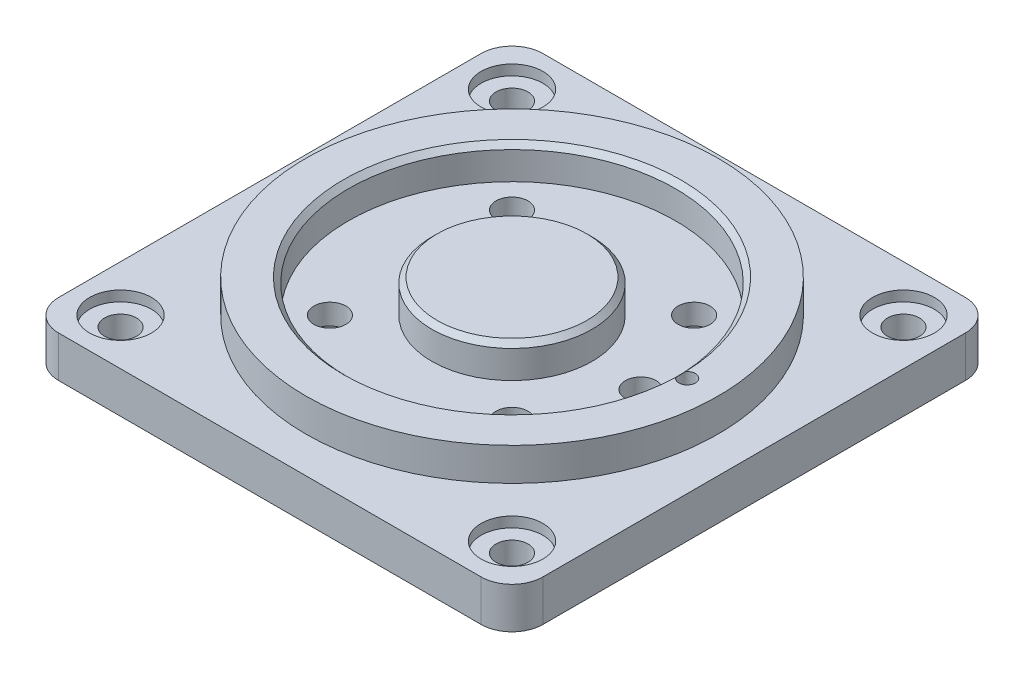
SolidWorks part; units mm, degrees
ref_plane "Front Plane" through (0, 0, 0) normal (0, 0, 1) x (1, 0, 0)
ref_plane "Top Plane" through (0, 0, 0) normal (0, 1, 0) x (1, 0, 0)
ref_plane "Right Plane" through (0, 0, 0) normal (1, 0, 0) x (0, 0, -1)
sketch "Sketch1" plane through (0, 0, 0) normal (0, 1, 0) x (1, 0, 0)
  line L0 (0, 34) -> (0, 0) construction
  line L1 (34, 0) -> (0, 0) construction
  line L2 (0, 0) -> (-25, 0) construction
  line L3 (17.6777, -17.6777) -> (0, 0) construction
  line L5 (-47, 47) -> (47, 47)
  line L6 (-47, 47) -> (-47, -47)
  line L7 (-47, -47) -> (47, -47)
  line L8 (47, 47) -> (47, -47)
  line L9 (-47, 47) -> (47, -47) construction
  line L10 (-47, -47) -> (47, 47) construction
  circle A0 centre (0, 0) radius 40 construction
  circle A1 centre (0, 0) radius 34 construction
  circle A2 centre (0, 34) radius 1.6 construction
  circle A3 centre (24.0416, 24.0416) radius 1.6 construction
  circle A4 centre (34, 0) radius 1.6 construction
  circle A5 centre (24.0416, -24.0416) radius 1.6 construction
  circle A6 centre (0, -34) radius 1.6 construction
  circle A7 centre (-24.0416, -24.0416) radius 1.6 construction
  circle A8 centre (-34, 0) radius 1.6 construction
  circle A9 centre (-24.0416, 24.0416) radius 1.6 construction
  circle A10 centre (34, 0) radius 1.6
  circle A11 centre (0, 0) radius 25 construction
  circle A12 centre (17.6777, -17.6777) radius 3.1
  circle A16 centre (25, 0) radius 3
  circle A17 centre (-17.6777, -17.6777) radius 3.1
  circle A18 centre (-17.6777, 17.6777) radius 3.1
  circle A19 centre (17.6777, 17.6777) radius 3.1
  point P22 (0, 0)
  point P32 (25, 0)
  point P39 (0, 0)
  dimension "D1" = 80
  dimension "D2" = 68
  dimension "D4" = 3.2
  dimension "D5" = 3.2
  dimension "D7" = 6
  dimension "D8" = 50
  dimension "D10" = 6.2
  dimension "D6" = 90
  dimension "D9" = 45
  dimension "D12" = 94
  dimension "D13" = 94
  dimension "D3" = 8
  dimension "D11" = 4
extrude "Boss-Extrude1" add sketch "Sketch1" along normal blind 8
sketch "Sketch2" plane through (0, 0, 0) normal (0, -1, 0) x (1, 0, 0)
  circle A0 centre (17.6777, 17.6777) radius 7
  circle A4 centre (17.6777, -17.6777) radius 7
  circle A5 centre (-17.6777, -17.6777) radius 7
  circle A6 centre (-17.6777, 17.6777) radius 7
  point P15 (0, 0)
  dimension "D1" = 14
  dimension "D2" = 4
extrude "Cut-Extrude1" cut sketch "Sketch2" against normal blind 4
sketch "Sketch3" plane through (0, 8, 0) normal (0, 1, 0) x (1, 0, 0)
  circle A0 centre (0, 0) radius 15.55
  circle A1 centre (0, 0) radius 31.75
  circle A2 centre (0, 0) radius 40
  dimension "D1" = 31.1
  dimension "D2" = 63.5
  dimension "D3" = 80
extrude "Boss-Extrude2" add sketch "Sketch3" along normal blind 6.4
chamfer "Chamfer1" distance 1 angle 45 2 edges at (0, 14.4, 15.55) (0, 14.4, 31.75)
fillet "Fillet1" radius 6 4 edges at (-47, 4, 47) (47, 4, 47) (47, 4, -47) (-47, 4, -47)
sketch "Sketch5" plane through (0, 8, 0) normal (0, 1, 0) x (1, 0, 0)
  line L0 (-38, 38) -> (0, 0) construction
  line L1 (0, 0) -> (0, 9.4707) construction
  circle A0 centre (-38, 38) radius 3.1
  circle A2 centre (38, 38) radius 3.1
  circle A3 centre (38, -38) radius 3.1
  circle A4 centre (-38, -38) radius 3.1
  point P14 (0, 0)
  dimension "D1" = 6.2
  dimension "D2" = 45
  dimension "D3" = 38
  dimension "D4" = 4
extrude "Cut-Extrude2" cut sketch "Sketch5" against normal through all
sketch "Sketch6" plane through (0, 8, 0) normal (0, 1, 0) x (1, 0, 0)
  circle A0 centre (-38, 38) radius 6
  circle A1 centre (38, 38) radius 6
  circle A2 centre (38, -38) radius 6
  circle A3 centre (-38, -38) radius 6
  point P12 (0, 0)
  dimension "D1" = 12
  dimension "D2" = 4
extrude "Cut-Extrude3" cut sketch "Sketch6" against normal blind 2
